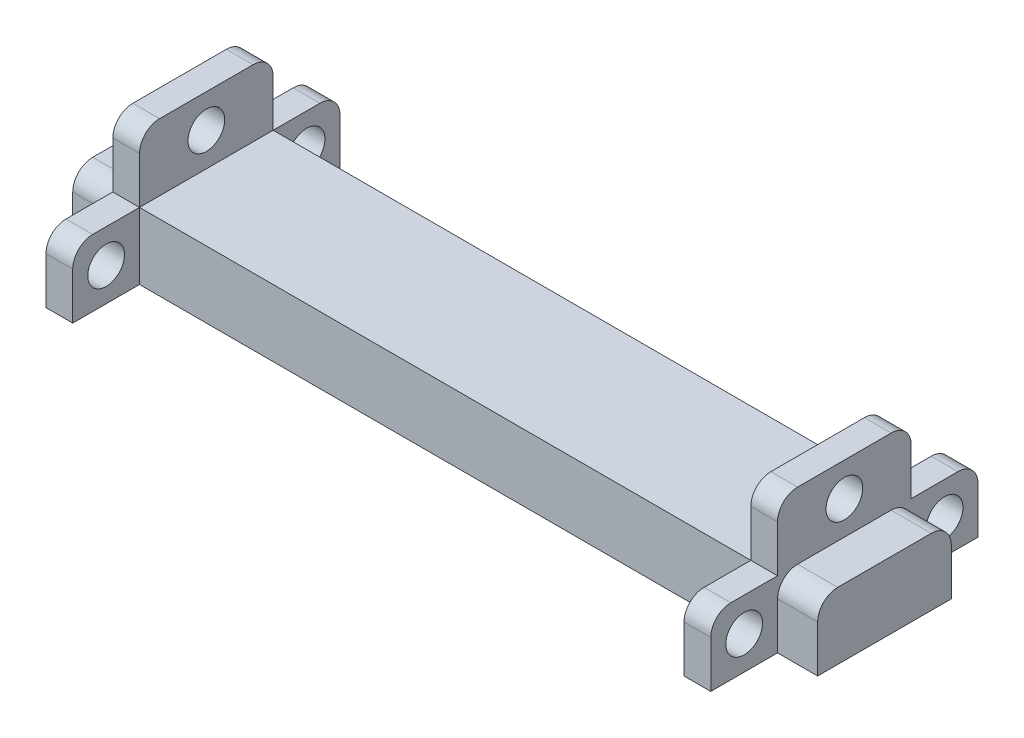
SolidWorks part; units mm, degrees
ref_plane "前视基准面" through (0, 0, 0) normal (0, 0, 1) x (1, 0, 0)
ref_plane "上视基准面" through (0, 0, 0) normal (0, 1, 0) x (1, 0, 0)
ref_plane "右视基准面" through (0, 0, 0) normal (1, 0, 0) x (0, 0, -1)
other "Configuration Table"
sketch "草图2" plane through (0, 0, 0) normal (1, 0, 0) x (0, 0, -1)
  line L1 (-10, -5) -> (10, -5)
  line L2 (-10, -5) -> (-10, 5)
  line L3 (-10, 5) -> (10, 5)
  line L4 (10, -5) -> (10, 5)
  line L5 (-10, -5) -> (10, 5) construction
  line L6 (-10, 5) -> (10, -5) construction
  point P0 (0, 0)
  dimension "D1" = 20
  dimension "D2" = 10
extrude "凸台-拉伸1" add sketch "草图2" along normal mid plane 111.5
ref_plane "基准面1" through (49.75, 0, 0) normal (1, 0, 0) x (0, 0, -1)
sketch "草图3" plane through (49.75, 0, 0) normal (1, 0, 0) x (0, 0, -1)
  line L0 (0, -5) -> (0, 10) construction
  line L1 (-10, -5) -> (10, -5) construction
  line L2 (-15, 0) -> (15, 0) construction
  line L3 (10, 5) -> (-10, 5) construction
  line L4 (-10, -5) -> (-20, -5)
  line L5 (-10, -5) -> (-10, 5)
  line L6 (-10, 5) -> (-20, 5)
  line L7 (-20, -5) -> (-20, 5)
  line L9 (10, -5) -> (20, -5)
  line L10 (10, -5) -> (10, 5)
  line L11 (10, 5) -> (20, 5)
  line L12 (20, -5) -> (20, 5)
  line L13 (-10, 5) -> (10, 5)
  line L14 (-10, 5) -> (-10, 15)
  line L15 (-10, 15) -> (10, 15)
  line L16 (10, 5) -> (10, 15)
  circle A0 centre (-15, 0) radius 2.75
  circle A1 centre (15, 0) radius 2.75
  circle A2 centre (0, 10) radius 2.75
  dimension "D1" = 5.5
  dimension "D2" = 30
  dimension "D3" = 15
  dimension "D4" = 10
  dimension "D5" = 10
  dimension "D6" = 10
extrude "凸台-拉伸2" add sketch "草图3" against normal blind 4 contours L13 L16 L15 L14 A2 | L9 L12 L11 L10 A1 | L7 L4 L5 L6 A0 region at (49.75, 4.8586, -15) region at (49.75, 10, 9.7764) region at (49.75, -4.8586, 15)
fillet "圆角1" radius 3 4 edges at (47.75, 5, -20) (47.75, 15, -10) (47.75, 15, 10) (47.75, 5, 20)
mirror "镜向1" about plane through (0, 0, 0) normal (1, 0, 0) of "圆角1", "凸台-拉伸2"
fillet "圆角2" radius 3 4 edges at (-52.75, 5, 10) (-52.75, 5, -10) (52.75, 5, 10) (52.75, 5, -10)
